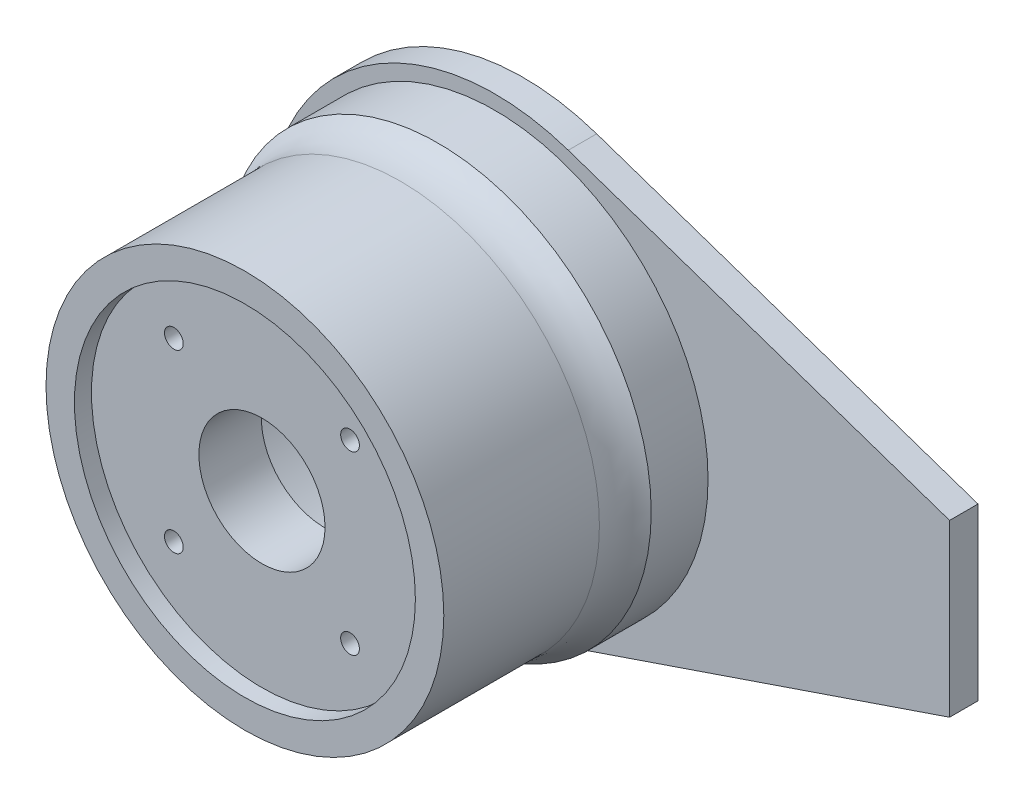
SolidWorks part; units mm, degrees
ref_plane "Plan de face" through (0, 0, 0) normal (0, 0, 1) x (1, 0, 0)
ref_plane "Plan de dessus" through (0, 0, 0) normal (0, 1, 0) x (1, 0, 0)
ref_plane "Plan de droite" through (0, 0, 0) normal (1, 0, 0) x (0, 0, -1)
sketch "Esquisse1" plane through (0, 0, 0) normal (0, 0, 1) x (1, 0, 0)
  circle A0 centre (0, 0) radius 35
  circle A1 centre (0, 0) radius 11.1
  circle A2 centre (-15.5, 15.5) radius 1.65
  circle A3 centre (15.5, 15.5) radius 1.65
  circle A4 centre (15.5, -15.5) radius 1.65
  circle A5 centre (-15.5, -15.5) radius 1.65
  point P9 (-60, 0)
  point P22 (0, 0)
  dimension "D1" = 70
  dimension "D2" = 22.2
  dimension "D7" = 3.3
  dimension "D5" = 15.5
  dimension "D8" = 4
extrude "Boss.-Extru.1" add sketch "Esquisse1" along normal blind 14 contours A0 A1 A2 A3 | A0 A1 A5 A4 | A0 | A0 region at (-34.0101, 0, 0)
sketch "Esquisse2" plane through (0, 0, 0) normal (0, 0, -1) x (-1, 0, 0)
  circle A1 centre (0, 0) radius 35
  circle A2 centre (0, 0) radius 29.9055
  dimension "D2" = 70
extrude "Boss.-Extru.5" add sketch "Esquisse2" along normal blind 20
sketch "Esquisse5" plane through (0, 0, -20) normal (0, 0, -1) x (-1, 0, 0)
  circle A0 centre (0, 0) radius 29.9055
  circle A1 centre (0, 0) radius 37.5
  dimension "D1" = 75
extrude "Boss.-Extru.6" add sketch "Esquisse5" along normal blind 10
fillet "Congé1" radius 10 1 edges at (-35, 0, -20)
sketch "Esquisse6" plane through (0, 0, -30) normal (0, 0, -1) x (-1, 0, 0)
  line L0 (-1000, 0) -> (49000, 0) construction
  line L1 (-12.9008, 37.8625) -> (-80, 15)
  line L2 (-80, 15) -> (-80, -15)
  line L3 (-12.9008, -37.8625) -> (-80, -15)
  circle A0 centre (0, 0) radius 29.9055
  arc A1 (-12.9008, -37.8625) -> (-12.9008, 37.8625) centre (0, 0) ccw
  point P11 (-80, 0)
  dimension "D1" = 80
  dimension "D2" = 80
  dimension "D3" = 15
extrude "Boss.-Extru.7" add sketch "Esquisse6" along normal blind 5
sketch "Esquisse7" plane through (0, 0, 14) normal (0, 0, 1) x (1, 0, 0)
  circle A0 centre (0, 0) radius 30
  dimension "D1" = 60
extrude "Enlèv. mat.-Extru.1" cut sketch "Esquisse7" against normal blind 3
